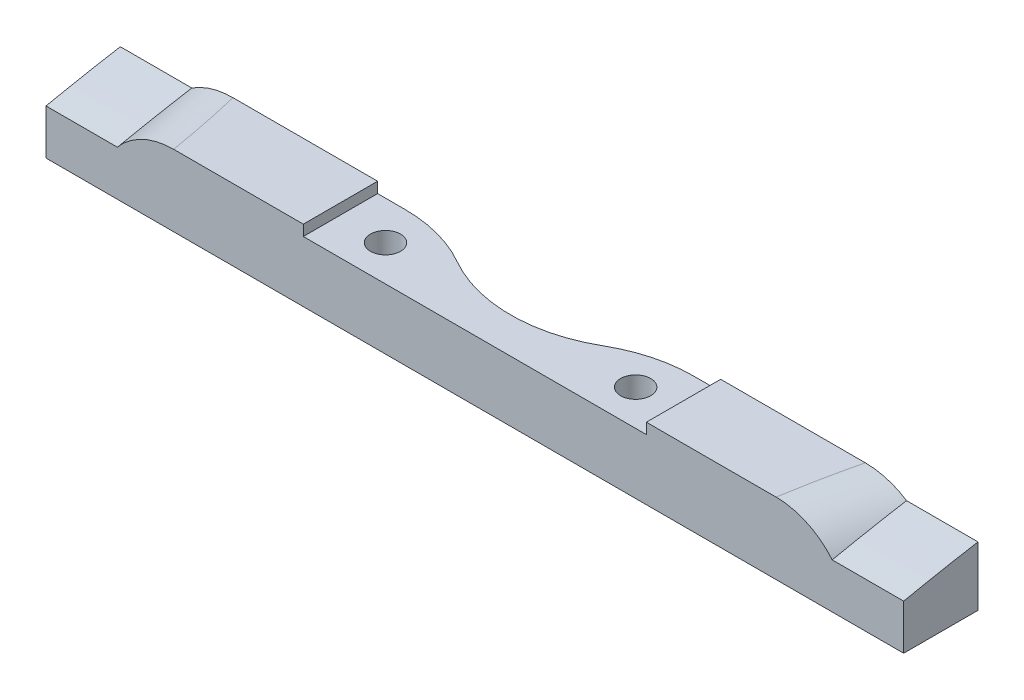
SolidWorks part; units mm, degrees
ref_plane "Ebene vorne" through (0, 0, 0) normal (0, 0, 1) x (1, 0, 0)
ref_plane "Ebene oben" through (0, 0, 0) normal (0, 1, 0) x (1, 0, 0)
ref_plane "Ebene rechts" through (0, 0, 0) normal (1, 0, 0) x (0, 0, -1)
sketch "Skizze1" plane through (0, 0, 0) normal (0, 1, 0) x (1, 0, 0)
  line L0 (-60, 0) -> (60, 0)
  line L1 (60, 0) -> (60, 10.4)
  line L2 (60, 10.4) -> (13.8609, 10.4)
  line L3 (0, 10) -> (0, 0) construction
  line L4 (-60, 0) -> (-60, 10.4)
  line L5 (-13.8609, 10.4) -> (-60, 10.4)
  arc A0 (13.8609, 10.4) -> (0, 5) centre (0, 25.4893) cw
  arc A1 (-13.8609, 10.4) -> (0, 5) centre (0, 25.4893) ccw
  dimension "D3" = 5
  dimension "D1" = 120
  dimension "D2" = 10.4
extrude "Aufsatz-Linear austragen1" add sketch "Skizze1" along normal blind 10
sketch "Skizze3" plane through (0, 10, 0) normal (0, 1, 0) x (1, 0, 0)
  line L0 (0, 0) -> (0, 22.3064) construction
  line L1 (17.5, 5) -> (-17.5, 5) construction
  line L2 (0, 13) -> (0, 5) construction
  circle A0 centre (17.5, 5) radius 2.1
  circle A1 centre (0, 13) radius 2.5 construction
  circle A2 centre (-17.5, 5) radius 2.1
  arc A3 (-13.8609, 10.4) -> (13.8609, 10.4) centre (0, 25.4893) ccw construction
  dimension "D1" = 4.2
  dimension "D4" = 5
  dimension "D2" = 35
  dimension "D3" = 8
  dimension "D5" = 8
extrude "Schnitt-Linear austragen1" cut sketch "Skizze3" against normal blind 10 contours A0 | A2 region at (17.5, 10, -5)
sketch "Skizze4" plane through (-60, 0, 0) normal (1, 0, 0) x (0, 0, -1)
  line L0 (0, 10) -> (10.4, 10)
  line L1 (10.4, 10) -> (10.4, 8.2965)
  line L2 (10.4, 10) -> (10.4, 0) construction
  line L3 (0, 10) -> (0, 6.32)
  line L4 (0, 10) -> (0, 0) construction
  arc A1 (0, 6.32) -> (10.4, 8.2965) centre (58.0172, -270.6068) cw
extrude "Schnitt-Linear austragen2" cut sketch "Skizze4" along normal blind 10
fillet "Verrundung1" radius 10 1 edges at (-50, 10, -5.2)
mirror "Spiegeln1" about plane through (0, 0, 0) normal (1, 0, 0) of "Schnitt-Linear austragen2", "Verrundung1"
sketch "Skizze5" plane through (0, 10, 0) normal (0, 1, 0) x (1, 0, 0)
  circle A0 centre (-17.5, 5) radius 3.65
  circle A1 centre (17.5, 5) radius 3.65
  dimension "D1" = 7.3
extrude "Schnitt-Linear austragen3" [suppressed] cut sketch "Skizze5" against normal blind 3
fillet "Verrundung2" radius 20 2 edges at (13.8609, 5, -10.4) (-13.8609, 5, -10.4)
sketch "Skizze7" plane through (0, 0, 0) normal (0, -1, 0) x (1, 0, 0)
  circle A0 centre (-17.5, -5) radius 3.65
  circle A1 centre (17.5, -5) radius 3.65
  dimension "D1" = 7.3
extrude "Schnitt-Linear austragen5" cut sketch "Skizze7" against normal blind 3
sketch "Skizze8" plane through (0, 10, 0) normal (0, 1, 0) x (1, 0, 0)
  line L1 (-24, -5.386) -> (24, -5.386)
  line L2 (-24, -5.386) -> (-24, 12.7441)
  line L3 (-24, 12.7441) -> (24, 12.7441)
  line L4 (24, -5.386) -> (24, 12.7441)
  line L5 (-24, -5.386) -> (24, 12.7441) construction
  line L6 (-24, 12.7441) -> (24, -5.386) construction
  point P0 (0, 3.679)
  dimension "D1" = 48
extrude "Schnitt-Linear austragen6" cut sketch "Skizze8" against normal blind 1.5
sketch "Skizze6" plane through (0, 0, 0) normal (0, -1, 0) x (1, 0, 0)
  line L1 (-24.9478, 11.0453) -> (24.9478, 11.0453)
  line L2 (-24.9478, 11.0453) -> (-24.9478, -11.0453)
  line L3 (-24.9478, -11.0453) -> (24.9478, -11.0453)
  line L4 (24.9478, 11.0453) -> (24.9478, -11.0453)
  line L5 (-24.9478, 11.0453) -> (24.9478, -11.0453) construction
  line L6 (-24.9478, -11.0453) -> (24.9478, 11.0453) construction
  point P0 (0, 0)
extrude "Schnitt-Linear austragen4" [suppressed] cut sketch "Skizze6" against normal blind 2.5
